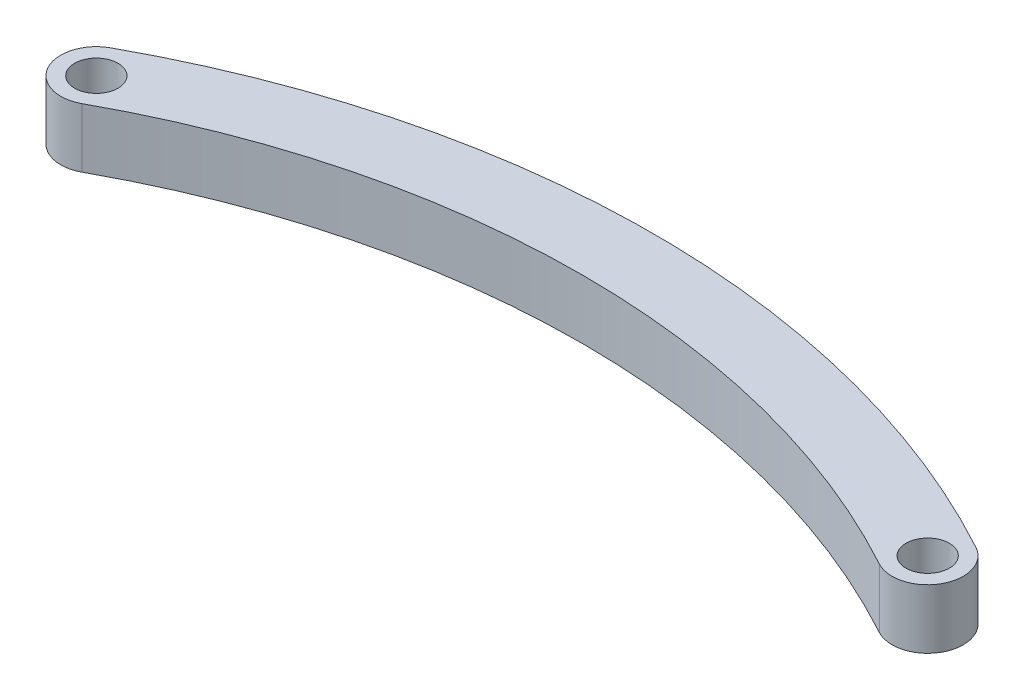
SolidWorks part; units mm, degrees
ref_plane "Front Plane" through (0, 0, 0) normal (0, 0, 1) x (1, 0, 0)
ref_plane "Top Plane" through (0, 0, 0) normal (0, 1, 0) x (1, 0, 0)
ref_plane "Right Plane" through (0, 0, 0) normal (1, 0, 0) x (0, 0, -1)
sketch "Esquisse1" plane through (0, 0, 0) normal (0, 1, 0) x (1, 0, 0)
  line L0 (-35, 0) -> (0, 0) construction
  line L1 (0, 0) -> (35, 0) construction
  circle A0 centre (-35, 0) radius 1.825
  circle A1 centre (35, 0) radius 1.825
  circle A2 centre (-35, 0) radius 3
  circle A3 centre (35, 0) radius 3
  circle A4 centre (0, -64.0625) radius 70
  circle A5 centre (0, -64.0625) radius 76
  dimension "D2" = 3.65
  dimension "D3" = 6
  dimension "D4" = 140
  dimension "D5" = 152
  dimension "D1" = 35
extrude "Boss.-Extru.1" add sketch "Esquisse1" along normal blind 5 contours A3 A5 A2 A4 | A2 A0 | A3 A1 region at (-32.4928, 0, 1.4872) region at (0, 0, -6.3427) region at (37.5072, 0, -1.4872)
